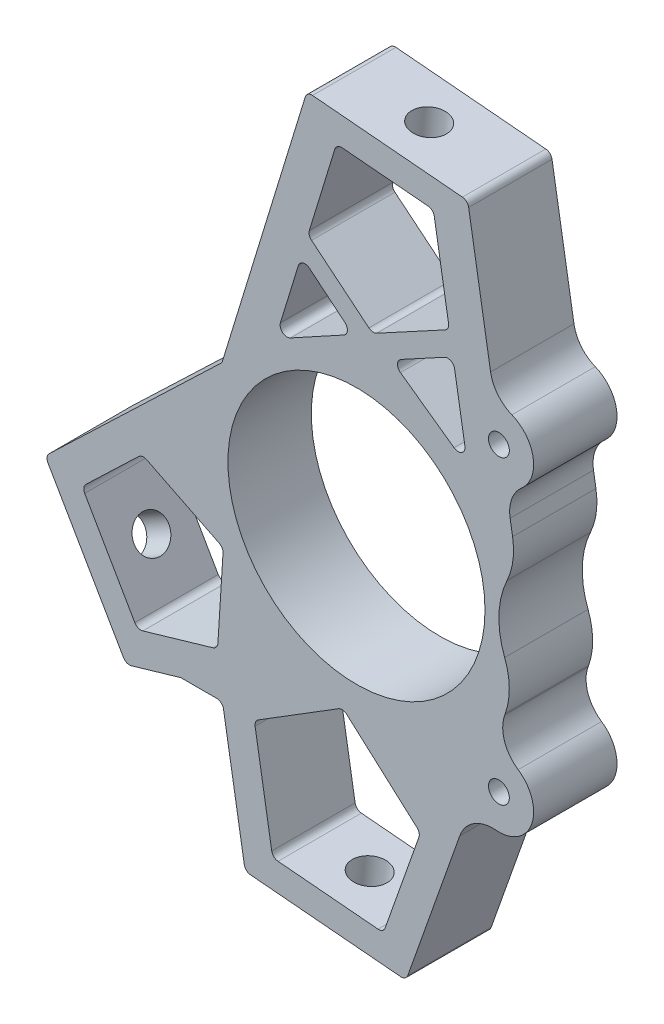
SolidWorks part; units mm, degrees
ref_plane "Front Plane" through (0, 0, 0) normal (0, 0, 1) x (1, 0, 0)
ref_plane "Top Plane" through (0, 0, 0) normal (0, 1, 0) x (1, 0, 0)
ref_plane "Right Plane" through (0, 0, 0) normal (1, 0, 0) x (0, 0, -1)
sketch "Sketch1" plane through (0, 0, 0) normal (0, 0, 1) x (1, 0, 0)
  circle A0 centre (0, 0) radius 57.5 construction
  circle A1 centre (0, 0) radius 40 construction
  dimension "D1" = 115
  dimension "D2" = 80
sketch "Sketch2" plane through (0, 0, 0) normal (0, 0, 1) x (1, 0, 0)
  line L0 (0, 0) -> (-81.4302, 0) construction
  line L1 (0, 0) -> (4.1835, 47.8173) construction
  line L2 (0, 0) -> (-4.1835, -47.8173) construction
  line L3 (0, 0) -> (-36.5058, -21.0766) construction
  line L4 (16.0197, 49.7933) -> (23.6724, 3.9519)
  line L5 (-7.1298, 51.8186) -> (-21.0344, 6.4461)
  line L6 (22.6265, -8.0025) -> (7.1298, -51.8186)
  line L7 (-23.6724, -3.9519) -> (-16.0197, -49.7933)
  line L8 (-15.2058, 15.8992) -> (-44.7999, -12.4044)
  line L9 (-33.1424, -32.5956) -> (6.1662, -21.1182)
  line L11 (7.1298, -51.8186) -> (-16.0197, -49.7933)
  line L12 (-33.1424, -32.5956) -> (-44.7999, -12.4044)
  line L13 (16.0197, 49.7933) -> (-7.1298, 51.8186)
  line L14 (-25.2742, -30.2982) -> (-19.2742, -30.2982)
  circle A0 centre (0, 0) radius 22
  circle A1 centre (4.1835, 47.8173) radius 6 construction
  circle A2 centre (-4.1835, -47.8173) radius 6 construction
  circle A5 centre (-4.1835, -47.8173) radius 12 construction
  circle A7 centre (4.1835, 47.8173) radius 12 construction
  circle A9 centre (-36.5058, -21.0766) radius 12 construction
  circle A10 centre (0, 0) radius 18.5
  circle A11 centre (0, 0) radius 24
  dimension "D1" = 44
  dimension "D2" = 95
  dimension "D3" = 12
  dimension "D7" = 12
  dimension "D8" = 45
  dimension "D11" = 48
  dimension "D13" = 24
  dimension "D14" = 6
  dimension "D15" = 24
  dimension "D17" = 24
  dimension "D18" = 37
  dimension "D4" = 51
  dimension "D5" = 51
  dimension "D6" = 85
  dimension "D10" = 30
  dimension "D19" = 90
extrude "Boss-Extrude1" add sketch "Sketch2" along normal blind 12 contours A7 A1 | A1 | A5 | A2 | A5 A2 | A5 | A11 L4 L13 L5 | A11 L5 L8 A0 L9 | A10 | A0 A10 | L8 A11 L9 A0 L5 | A0 L8 L5 | A11 L8 L12 L9 L7 | A11 L7 L9 | A11 L9 L7 L11 L6 | L9 L14 L7 region at (3.6941, 34.3446, 0) region at (23.2734, 1.9293, 0) region at (-1.0717, -35.8766, 0) region at (-18.8543, 11.6253, 0) region at (-20.6409, 9.3265, 0) region at (-30.5343, -14.9888, 0) region at (-15.9856, -21.4912, 0) region at (-18.1968, 11.2199, 0) region at (-21.3671, -29.7414, 0) region at (0, 0, 0)
extrude "Cut-Extrude1" cut sketch "Sketch2<5>" along normal through all contours A10 region at (0, 0, 0)
sketch "Sketch2<5>" plane through (0, 0, 0) normal (0, 0, 1) x (1, 0, 0) same geometry as "Sketch2"
sketch "Sketch4" plane through (0, 0, 0) normal (0, 0, -1) x (-1, 0, 0)
  line L0 (-16.0197, 49.7933) -> (7.1298, 51.8186)
  line L1 (7.1298, 51.8186) -> (19.353, 11.9328)
  line L2 (19.353, 11.9328) -> (44.7999, -12.4044)
  line L3 (44.7999, -12.4044) -> (33.1424, -32.5956)
  line L4 (33.1424, -32.5956) -> (25.2742, -30.2982)
  line L5 (25.2742, -30.2982) -> (19.2742, -30.2982)
  line L6 (19.2742, -30.2982) -> (16.0197, -49.7933)
  line L7 (16.0197, -49.7933) -> (-7.1298, -51.8186)
  line L8 (-7.1298, -51.8186) -> (-22.6265, -8.0025)
  line L9 (-16.0197, 49.7933) -> (-23.6724, 3.9519)
  line L10 (0, 0) -> (38.9711, -22.5) construction
  line L11 (0, 0) -> (4.4449, -50.8059) construction
  line L12 (0, 0) -> (-4.4449, 50.8059) construction
  line L17 (39.1144, -14.2518) -> (31.8996, -26.7482)
  line L18 (39.507, -13.5718) -> (32.5788, -9.5718) construction
  line L19 (31.507, -27.4282) -> (24.5788, -23.4282) construction
  line L20 (32.5788, -9.5718) -> (24.5788, -23.4282) construction
  line L28 (11.2942, -46.1914) -> (-3.1016, -47.4509)
  line L29 (12.0659, -46.1239) -> (11.3686, -38.1543) construction
  line L30 (-3.8732, -47.5184) -> (-4.5705, -39.5488) construction
  line L31 (11.3686, -38.1543) -> (-4.5705, -39.5488) construction
  line L39 (2.0709, 47.3607) -> (-10.298, 46.2786)
  line L40 (2.877, 47.4312) -> (3.5743, 39.4617) construction
  line L41 (-11.0697, 46.2111) -> (-10.3724, 38.2415) construction
  line L42 (3.5743, 39.4617) -> (-10.3724, 38.2415) construction
  line L46 (2.877, 47.4312) -> (-10.3724, 38.2415) construction
  line L47 (-11.0697, 46.2111) -> (3.5743, 39.4617) construction
  line L48 (3.1142, 46.6575) -> (6.783, 34.6856)
  line L49 (-11.1972, 45.447) -> (-13.2575, 33.1058)
  line L50 (-12.7478, 32.0621) -> (-2.9019, 26.7232)
  line L51 (-1.7898, 26.8301) -> (6.4623, 33.6204)
  line L52 (-13.3749, 32.4022) -> (-16.0095, 16.6206) construction
  line L53 (-16.0095, 16.6206) -> (-2.3099, 26.4022) construction
  line L54 (6.9791, 34.0457) -> (11.6672, 18.7479) construction
  line L55 (11.6672, 18.7479) -> (-2.3099, 26.4022) construction
  line L56 (-12.6651, 28.6046) -> (-6.4334, 25.2254)
  line L57 (1.6664, 25.789) -> (6.7762, 29.9937)
  line L58 (-14.1282, 27.8902) -> (-15.6119, 19.0021)
  line L59 (8.3677, 29.5145) -> (10.9466, 21.0993)
  line L60 (-6.329, 23.5325) -> (-14.0445, 18.0236)
  line L61 (1.8215, 24.1397) -> (9.5102, 19.9292)
  line L62 (12.0659, -46.1239) -> (-4.5705, -39.5488) construction
  line L63 (-3.8732, -47.5184) -> (11.3686, -38.1543) construction
  line L64 (-4.1315, -46.7881) -> (-8.9848, -33.0657)
  line L65 (-8.709, -31.9872) -> (1.4046, -22.9336)
  line L66 (2.5991, -22.8291) -> (14.1312, -29.9889)
  line L67 (14.5901, -31.0031) -> (12.1934, -45.3599)
  line L68 (39.507, -13.5718) -> (24.5788, -23.4282) construction
  line L69 (31.507, -27.4282) -> (32.5788, -9.5718) construction
  line L70 (30.7533, -27.2081) -> (20.6614, -24.2615)
  line L71 (19.9437, -23.3647) -> (19.2069, -11.7285)
  line L72 (19.7606, -10.7694) -> (30.2063, -5.5894)
  line L73 (31.3418, -5.7626) -> (38.9396, -13.0291)
  arc A0 (-23.6724, 3.9519) -> (-22.6265, -8.0025) centre (0, 0) ccw
  arc A1 (-23.6724, 3.9519) -> (-22.6265, -8.0025) centre (0, 0) ccw construction
  arc A23 (-10.298, 46.2786) -> (-11.1972, 45.447) centre (-10.2109, 45.2824) ccw
  arc A24 (2.0709, 47.3607) -> (3.1142, 46.6575) centre (2.158, 46.3645) cw
  arc A25 (6.783, 34.6856) -> (6.4623, 33.6204) centre (5.8269, 34.3926) cw
  arc A26 (-13.2575, 33.1058) -> (-12.7478, 32.0621) centre (-12.2711, 32.9412) ccw
  arc A27 (-2.9019, 26.7232) -> (-1.7898, 26.8301) centre (-2.4252, 27.6023) ccw
  arc A28 (10.9466, 21.0993) -> (9.5102, 19.9292) centre (9.9905, 20.8062) cw
  arc A29 (6.7762, 29.9937) -> (8.3677, 29.5145) centre (7.4116, 29.2215) cw
  arc A30 (1.6664, 25.789) -> (1.8215, 24.1397) centre (2.3018, 25.0168) ccw
  arc A31 (-6.4334, 25.2254) -> (-6.329, 23.5325) centre (-6.91, 24.3464) cw
  arc A32 (-15.6119, 19.0021) -> (-14.0445, 18.0236) centre (-14.6256, 18.8374) ccw
  arc A33 (-12.6651, 28.6046) -> (-14.1282, 27.8902) centre (-13.1418, 27.7255) ccw
  arc A34 (19.2069, -11.7285) -> (19.7606, -10.7694) centre (20.2049, -11.6653) cw
  arc A35 (30.2063, -5.5894) -> (31.3418, -5.7626) centre (30.6506, -6.4853) cw
  arc A36 (38.9396, -13.0291) -> (39.1144, -14.2518) centre (38.2484, -13.7518) cw
  arc A37 (31.8996, -26.7482) -> (30.7533, -27.2081) centre (31.0336, -26.2482) cw
  arc A38 (20.6614, -24.2615) -> (19.9437, -23.3647) centre (20.9417, -23.3015) cw
  arc A39 (-3.1016, -47.4509) -> (-4.1315, -46.7881) centre (-3.1887, -46.4547) cw
  arc A40 (12.1934, -45.3599) -> (11.2942, -46.1914) centre (11.2071, -45.1952) cw
  arc A41 (14.1312, -29.9889) -> (14.5901, -31.0031) centre (13.6038, -30.8385) cw
  arc A42 (-8.9848, -33.0657) -> (-8.709, -31.9872) centre (-8.0421, -32.7322) cw
  arc A43 (1.4046, -22.9336) -> (2.5991, -22.8291) centre (2.0716, -23.6787) cw
  point P33 (32.0429, -18.5)
  point P36 (19.1649, -11.0648)
  point P39 (30.8348, -5.2777)
  point P52 (19.988, -24.0648)
  point P63 (3.7477, -42.8364)
  point P66 (-3.7477, 42.8364)
  point P70 (14.7004, -30.3423)
  point P97 (-9.2082, -32.434)
  point P104 (1.9627, -22.434)
  point P122 (7.93, 30.943)
  point P125 (0.5249, 24.8497)
  point P128 (-5.0264, 24.4625)
  point P134 (-13.8973, 29.2728)
  dimension "D6" = 12
  dimension "D7" = 12
  dimension "D11" = 16
  dimension "D13" = 4
  dimension "D18" = 6
  dimension "D19" = 10
  dimension "D24" = 1
  dimension "D26" = 1
  dimension "D3" = 4
  dimension "D4" = 8
  dimension "D5" = 16
  dimension "D8" = 16
  dimension "D9" = 8
  dimension "D10" = 4
  dimension "D12" = 16
  dimension "D14" = 14
  dimension "D15" = 8
  dimension "D16" = 14
  dimension "D17" = 14
  dimension "D20" = 16
  dimension "D21" = 16
  dimension "D22" = 3
  dimension "D23" = 3
  dimension "D25" = 13
extrude "Cut-Extrude2" cut sketch "Sketch4" against normal through all contours L28 | L50 A27 L51 A25 L48 A24 L39 A23 L49 A26 | L56 A33 L58 A32 L60 A31 | L57 A30 L61 A28 L59 A29 | L17 A37 L70 A38 L71 A34 L72 A35 L73 A36 region at (-3.146, -35.9589, 0) region at (3.4448, 37.6067, 0) region at (11.6098, 23.5241, 0) region at (-6.6504, 24.9157, 0)
fillet "Fillet2" radius 1 8 edges at (7.1298, -51.8186, 6) (-16.0197, -49.7933, 6) (-25.2742, -30.2982, 6) (-19.2742, -30.2982, 6) (-33.1424, -32.5956, 6) (-44.7999, -12.4044, 6) (-7.1298, 51.8186, 6) (16.0197, 49.7933, 6)
sketch "Sketch5" plane through (-4.4449, -50.8059, 0) normal (-0.0872, -0.9962, 0) x (0.9962, -0.0872, 0)
  line L0 (-10.8444, 12) -> (10.8444, 0) construction
  line L1 (10.8444, 12) -> (-10.8444, 0) construction
  circle A0 centre (0, 6) radius 2.5
  dimension "D1" = 5
extrude "Cut-Extrude3" cut sketch "Sketch5" against normal blind 20
sketch "Sketch6" plane through (-38.9711, -22.5, 0) normal (-0.866, -0.5, 0) x (0.5, -0.866, 0)
  line L0 (-10.8723, 12) -> (10.8723, 0) construction
  circle A0 centre (0, 6) radius 2.5
  dimension "D1" = 5
extrude "Cut-Extrude4" cut sketch "Sketch6" against normal blind 20
sketch "Sketch7" plane through (4.4449, 50.8059, 0) normal (0.0872, 0.9962, 0) x (0.9962, -0.0872, 0)
  line L0 (-10.8097, 0) -> (10.8444, -12)
  circle A0 centre (0.0173, -6) radius 2.5
  dimension "D1" = 5
extrude "Cut-Extrude5" cut sketch "Sketch7" against normal blind 20 contours L0 A0 | L0 A0 region at (4.9745, 50.7596, 5.0719) region at (3.9499, 50.8492, 6.9281)
ref_axis "Axis1" through (0, 0, 12) along (0, 0, -1)
sketch "Sketch8" plane through (0, 0, 12) normal (0, 0, 1) x (1, 0, 0)
  line L0 (0, 0) -> (40, 0) construction
  line L1 (0, 0) -> (33, 0) construction
  line L2 (33, 0) -> (20.5, 21.6506) construction
  line L3 (17.7594, 20.4304) -> (23.3293, 7.9201)
  line L4 (22.9271, 23.414) -> (30.9763, 12.3351)
  line L5 (17.7594, -20.4304) -> (23.3293, -7.9201)
  line L6 (22.9271, -23.414) -> (30.9763, -12.3351)
  circle A0 centre (0, 0) radius 40 construction
  circle A1 centre (33, 0) radius 12.5
  circle A2 centre (20.5, 21.6506) radius 3
  circle A3 centre (20.5, -21.6506) radius 3
  circle A4 centre (20.5, 21.6506) radius 1.5
  circle A5 centre (20.5, 21.6506) radius 5
  circle A6 centre (20.5, -21.6506) radius 5
  circle A7 centre (20.5, -21.6506) radius 1.5
  dimension "D1" = 25
  dimension "D6" = 6
  dimension "D8" = 3
  dimension "D9" = 10
  dimension "D10" = 3
  dimension "D11" = 10
  dimension "D2" = 33
  dimension "D3" = 0
  dimension "D4" = 60
  dimension "D5" = 25
  dimension "D7" = 6
extrude "Cut-Extrude6" cut sketch "Sketch8" against normal blind 12 contours A2 A4 | A4 | A3 A7 | A7 region at (19.0424, 24.1752, 12) region at (21.1061, -18.7992, 12) region at (20.5, 21.6506, 12) region at (20.5, -21.6506, 12)
extrude "Boss-Extrude3" add sketch "Sketch8<5>" against normal blind 12 contours L3 A5 L4 A2 | L4 A5 L3 A2 | L5 A6 L6 A3 | L6 A6 L5 A3 region at (22.1702, 18.7577, 12) region at (18.4445, 18.5462, 12) region at (22.1702, -18.7577, 12) region at (18.4445, -18.5462, 12)
sketch "Sketch8<5>" plane through (0, 0, 12) normal (0, 0, 1) x (1, 0, 0) same geometry as "Sketch8"
extrude "Boss-Extrude4" add sketch "Sketch8<6>" against normal blind 3 contours A2 | A3
sketch "Sketch8<6>" plane through (0, 0, 12) normal (0, 0, 1) x (1, 0, 0) same geometry as "Sketch8"
extrude "Cut-Extrude7" cut sketch "Sketch8<7>" against normal blind 3 contours A4 | A7
sketch "Sketch8<7>" plane through (0, 0, 12) normal (0, 0, 1) x (1, 0, 0) same geometry as "Sketch8"
extrude "Cut-Extrude8" cut sketch "Sketch8<8>" against normal blind 12 contours A1 region at (33, 0, 12)
sketch "Sketch8<8>" plane through (0, 0, 12) normal (0, 0, 1) x (1, 0, 0) same geometry as "Sketch8"
fillet "Fillet3" radius 10 2 edges at (22.8598, -7.3094, 6) (23.0656, 7.5867, 6)
fillet "Fillet4" radius 5 4 edges at (16.6649, -24.8587, 6) (19.5346, -16.7447, 6) (19.8893, 26.6132, 6) (21.5344, 16.7588, 6)
